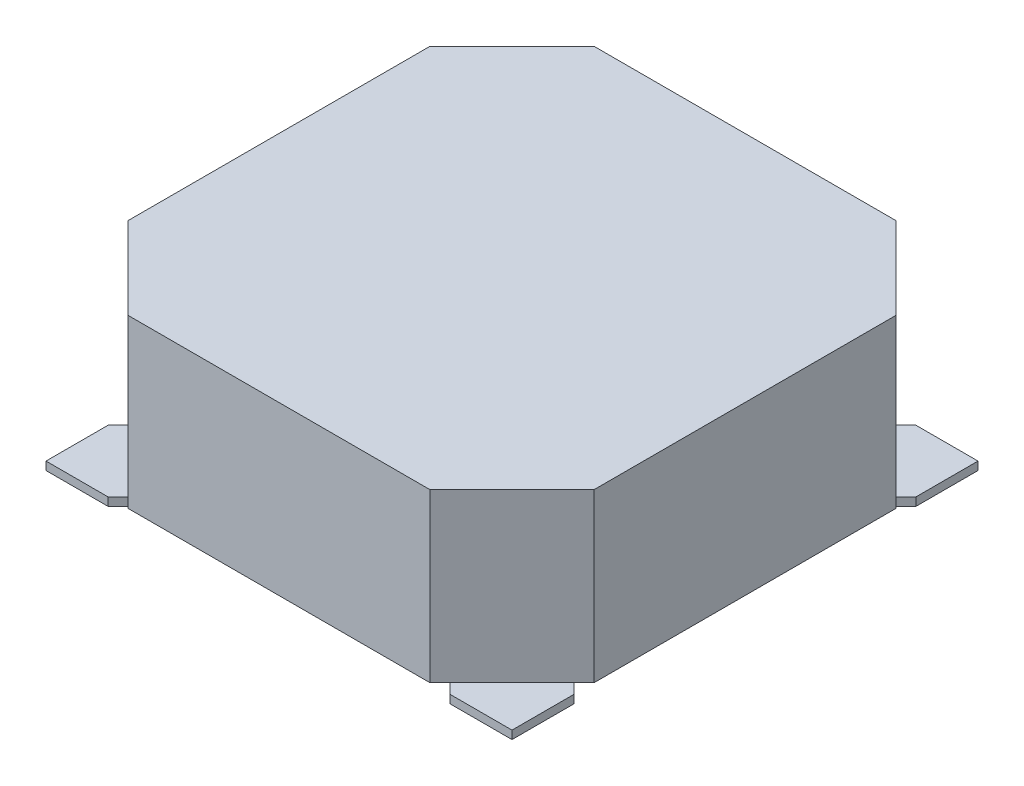
SolidWorks part; units mm, degrees
ref_plane "Front Plane" through (0, 0, 0) normal (0, 0, 1) x (1, 0, 0)
ref_plane "Top Plane" through (0, 0, 0) normal (0, 1, 0) x (1, 0, 0)
ref_plane "Right Plane" through (0, 0, 0) normal (1, 0, 0) x (0, 0, -1)
sketch "Sketch1" plane through (0, 0, 0) normal (0, 1, 0) x (1, 0, 0)
  line L1 (0, 0) -> (8.5, 0)
  line L2 (0, 0) -> (0, -8.5)
  line L3 (0, -8.5) -> (8.5, -8.5)
  line L4 (8.5, 0) -> (8.5, -8.5)
  dimension "D1" = 8.5
  dimension "D2" = 8.5
extrude "Boss-Extrude1" add sketch "Sketch1" along normal blind 3.2
sketch "Sketch2" plane through (0, 3.2, 0) normal (0, 1, 0) x (1, 0, 0)
  line L0 (1.5, 0) -> (0, -1.5)
  line L1 (8.5, -1.5) -> (7, 0)
  line L2 (7, -8.5) -> (8.5, -7)
  line L3 (0, -7) -> (1.5, -8.5)
  line L4 (0, 0) -> (0, -8.5)
  line L5 (0, -8.5) -> (8.5, -8.5)
  line L6 (8.5, -8.5) -> (8.5, 0)
  line L7 (8.5, 0) -> (0, 0)
  line L8 (0, -1.5) -> (0, -7) construction
  line L9 (1.5, -8.5) -> (7, -8.5) construction
  line L10 (8.5, -7) -> (8.5, -1.5) construction
  line L11 (7, 0) -> (1.5, 0) construction
  line L12 (0, -1.5) -> (0, 0)
  line L13 (0, 0) -> (1.5, 0)
  line L14 (1.5, 0) -> (1.5506, 0.09)
  line L15 (7, 0) -> (8.5, 0)
  line L16 (8.5, -8.5) -> (8.5, 0) construction
  line L17 (8.5, 0) -> (0, 0) construction
  line L18 (8.5, 0) -> (8.5, -1.5)
  line L19 (8.5, -7) -> (8.5, -8.5)
  line L20 (8.5, -8.5) -> (7, -8.5)
  line L21 (1.5, -8.5) -> (0, -8.5)
  line L22 (0, -7) -> (0, -8.5)
  line M9 (0, 0) -> (0, -8.5)
  line M10 (0, -8.5) -> (8.5, -8.5)
  line M11 (8.5, -8.5) -> (8.5, 0)
  line M12 (8.5, 0) -> (0, 0)
  dimension "D2" = 1.5
  dimension "D3" = 45
  dimension "D4" = 1.5
  dimension "D5" = 45
  dimension "D6" = 1.5
  dimension "D7" = 45
  dimension "D8" = 1.5
  dimension "D9" = 45
  dimension "D1" = 0
extrude "Cut-Extrude1" cut sketch "Sketch2" against normal blind 3.05 contours L3 M9 M10 | L0 M12 M9 | L1 M11 M12 | L2 M10 M11 region at (0.5, 3.2, 0.5) region at (8, 3.2, 0.5) region at (0.5, 3.2, 8) region at (8, 3.2, 8)
sketch "Sketch3" plane through (0, 0, 0) normal (0, -1, 0) x (1, 0, 0)
  line L0 (8.5, 1.1314) -> (7.3686, 0) construction
  line L1 (8.5, 0) -> (0, 0) construction
  line L2 (7.3686, 0) -> (8.5, 0) construction
  line L3 (8.5, 0) -> (8.5, 1.1314) construction
  line L4 (8.5, 8.5) -> (8.5, 0) construction
  line L5 (8.5, 1.1314) -> (7.9697, 1.6617)
  line L6 (7.9697, 1.6617) -> (6.8383, 0.5303)
  line L7 (6.8383, 0.5303) -> (7.3686, 0)
  line L8 (8.5, 8.5) -> (0, 0) construction
  line L9 (8.5, 0) -> (0, 8.5) construction
  line L10 (1.1314, 0) -> (1.6617, 0.5303)
  line L11 (1.6617, 0.5303) -> (0.5303, 1.6617)
  line L12 (0.5303, 1.6617) -> (0, 1.1314)
  line L13 (0, 7.3686) -> (0.5303, 6.8383)
  line L14 (0.5303, 6.8383) -> (1.6617, 7.9697)
  line L15 (1.6617, 7.9697) -> (1.1314, 8.5)
  line L16 (7.3686, 8.5) -> (6.8383, 7.9697)
  line L17 (6.8383, 7.9697) -> (7.9697, 6.8383)
  line L18 (7.9697, 6.8383) -> (8.5, 7.3686)
  line L19 (8.5, 7.3686) -> (8.5, 1.1314)
  line L20 (7.3686, 0) -> (1.1314, 0)
  line L21 (0, 1.1314) -> (0, 7.3686)
  line L22 (1.1314, 8.5) -> (7.3686, 8.5)
  point P16 (4.25, 4.25)
  point P33 (4.25, 4.25)
  dimension "D1" = 1.6
  dimension "D2" = 45
  dimension "D3" = 0.75
  dimension "D4" = 4
extrude "Cut-Extrude2" cut sketch "Sketch3" against normal up to surface (0.15 mm away) up to face at (8, 0.15, 8)
